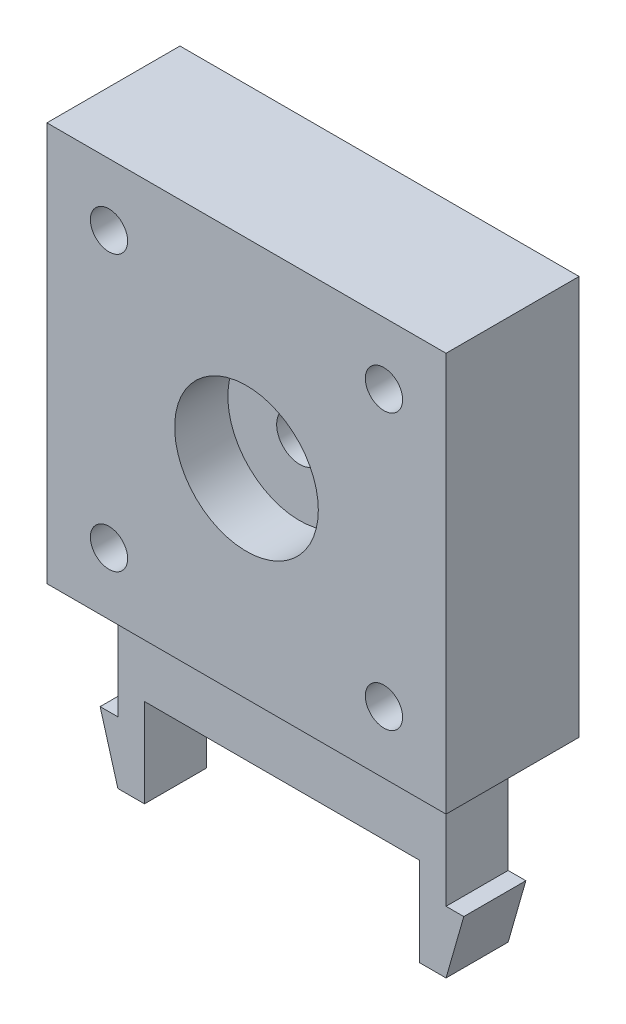
SolidWorks part; units mm, degrees
ref_plane "Front Plane" through (0, 0, 0) normal (0, 0, 1) x (1, 0, 0)
ref_plane "Top Plane" through (0, 0, 0) normal (0, 1, 0) x (1, 0, 0)
ref_plane "Right Plane" through (0, 0, 0) normal (1, 0, 0) x (0, 0, -1)
sketch "Sketch1" plane through (0, 0, 0) normal (0, 0, 1) x (1, 0, 0)
  line L1 (22.5, -22.5) -> (-22.5, -22.5)
  line L2 (22.5, -22.5) -> (22.5, 22.5)
  line L3 (22.5, 22.5) -> (-22.5, 22.5)
  line L4 (-22.5, -22.5) -> (-22.5, 22.5)
  line L5 (22.5, -22.5) -> (-22.5, 22.5) construction
  line L6 (22.5, 22.5) -> (-22.5, -22.5) construction
  circle A0 centre (0, 0) radius 2.6
  point P0 (0, 0)
  dimension "D3" = 5.2
  dimension "D1" = 45
  dimension "D2" = 45
extrude "Boss-Extrude1" add sketch "Sketch1" along normal mid plane 15
sketch "Sketch2" plane through (0, 0, 7.5) normal (0, 0, 1) x (1, 0, 0)
  circle A0 centre (0, 0) radius 8.1
  dimension "D1" = 16.2
extrude "Cut-Extrude1" cut sketch "Sketch2" against normal blind 6
sketch "Sketch5" plane through (0, 0, -7.5) normal (0, 0, -1) x (-1, 0, 0)
  circle A0 centre (0, 0) radius 8.1
  dimension "D1" = 16.2
extrude "Cut-Extrude4" cut sketch "Sketch5" against normal blind 6
sketch "Sketch6" plane through (0, 0, -7.5) normal (0, 0, 1) x (1, 0, 0)
  line L0 (19.2, 17.6362) -> (15.5, 19.7724)
  line L1 (15.5, -15.5) -> (-15.5, -15.5) construction
  line L2 (15.5, -15.5) -> (15.5, 15.5) construction
  line L3 (15.5, 15.5) -> (-15.5, 15.5) construction
  line L4 (-15.5, -15.5) -> (-15.5, 15.5) construction
  line L5 (15.5, -15.5) -> (-15.5, 15.5) construction
  line L6 (15.5, 15.5) -> (-15.5, -15.5) construction
  line L7 (-11.8, 17.6362) -> (-15.5, 19.7724)
  line L8 (-15.5, 19.7724) -> (-19.2, 17.6362)
  line L9 (-19.2, 17.6362) -> (-19.2, 13.3638)
  line L10 (-19.2, 13.3638) -> (-15.5, 11.2276)
  line L11 (-15.5, 11.2276) -> (-11.8, 13.3638)
  line L12 (-11.8, 13.3638) -> (-11.8, 17.6362)
  line L13 (15.5, 19.7724) -> (11.8, 17.6362)
  line L14 (11.8, 17.6362) -> (11.8, 13.3638)
  line L15 (11.8, 13.3638) -> (15.5, 11.2276)
  line L16 (15.5, 11.2276) -> (19.2, 13.3638)
  line L17 (19.2, 13.3638) -> (19.2, 17.6362)
  line L18 (19.2, -13.3638) -> (15.5, -11.2276)
  line L19 (15.5, -11.2276) -> (11.8, -13.3638)
  line L20 (11.8, -13.3638) -> (11.8, -17.6362)
  line L21 (11.8, -17.6362) -> (15.5, -19.7724)
  line L22 (15.5, -19.7724) -> (19.2, -17.6362)
  line L23 (19.2, -17.6362) -> (19.2, -13.3638)
  line L24 (-11.8, -13.3638) -> (-15.5, -11.2276)
  line L25 (-15.5, -11.2276) -> (-19.2, -13.3638)
  line L26 (-19.2, -13.3638) -> (-19.2, -17.6362)
  line L27 (-19.2, -17.6362) -> (-15.5, -19.7724)
  line L28 (-15.5, -19.7724) -> (-11.8, -17.6362)
  line L29 (-11.8, -17.6362) -> (-11.8, -13.3638)
  circle A4 centre (-15.5, 15.5) radius 3.7 construction
  circle A5 centre (15.5, 15.5) radius 3.7 construction
  circle A6 centre (15.5, -15.5) radius 3.7 construction
  circle A7 centre (-15.5, -15.5) radius 3.7 construction
  point P0 (0, 0)
  dimension "D2" = 2
  dimension "D1" = 31
  dimension "D3" = 7.4
  dimension "D4" = 2
sketch "Sketch7" plane through (0, -22.5, 0) normal (0, -1, 0) x (1, 0, 0)
  line L1 (18.5, -3.5) -> (-18.5, -3.5)
  line L2 (18.5, -3.5) -> (18.5, 3.5)
  line L3 (18.5, 3.5) -> (-18.5, 3.5)
  line L4 (-18.5, -3.5) -> (-18.5, 3.5)
  line L5 (18.5, -3.5) -> (-18.5, 3.5) construction
  line L6 (18.5, 3.5) -> (-18.5, -3.5) construction
  point P0 (0, 0)
  dimension "D1" = 37
  dimension "D2" = 7
extrude "Boss-Extrude2" add sketch "Sketch7" along normal blind 10
extrude "Cut-Extrude6" cut sketch "Sketch6" along normal blind 3.6 from offset 2
sketch "Sketch8" plane through (0, 0, -7.5) normal (0, 0, -1) x (-1, 0, 0)
  line L1 (15.5, -15.5) -> (-15.5, -15.5) construction
  line L2 (15.5, -15.5) -> (15.5, 15.5) construction
  line L3 (15.5, 15.5) -> (-15.5, 15.5) construction
  line L4 (-15.5, -15.5) -> (-15.5, 15.5) construction
  line L5 (15.5, -15.5) -> (-15.5, 15.5) construction
  line L6 (15.5, 15.5) -> (-15.5, -15.5) construction
  circle A0 centre (-15.5, 15.5) radius 2.1
  circle A1 centre (15.5, 15.5) radius 2.1
  circle A2 centre (15.5, -15.5) radius 2.1
  circle A3 centre (-15.5, -15.5) radius 2.1
  point P0 (0, 0)
  dimension "D2" = 4.2
  dimension "D1" = 31
  dimension "D3" = 2
  dimension "D4" = 2
extrude "Cut-Extrude7" cut sketch "Sketch8" against normal through all from offset 2 offset against normal yes
sketch "Sketch9" plane through (0, -32.5, 0) normal (0, -1, 0) x (1, 0, 0)
  line L0 (-18.5, -3.5) -> (18.5, -3.5) construction
  line L1 (-18.5, 3.5) -> (-15.5, 3.5)
  line L2 (-18.5, 3.5) -> (-18.5, -3.5)
  line L3 (-18.5, -3.5) -> (-15.5, -3.5)
  line L4 (-15.5, 3.5) -> (-15.5, -3.5)
  line L5 (0, 3.5) -> (0, -3.5) construction
  line L6 (18.5, 3.5) -> (-18.5, 3.5) construction
  line L7 (-18.5, -3.5) -> (18.5, -3.5) construction
  line L8 (15.5, 3.5) -> (15.5, -3.5)
  line L9 (18.5, -3.5) -> (15.5, -3.5)
  line L10 (18.5, 3.5) -> (18.5, -3.5)
  line L11 (18.5, 3.5) -> (15.5, 3.5)
  dimension "D1" = 3
extrude "Boss-Extrude3" add sketch "Sketch9" along normal blind 10
sketch "Sketch10" plane through (-18.5, 0, 0) normal (-1, 0, 0) x (0, 0, 1)
  line L0 (3.5, -42.5) -> (3.5, -22.5) construction
  line L1 (-3.5, -42.5) -> (3.5, -42.5)
  line L2 (-3.5, -42.5) -> (-3.5, -35.5)
  line L3 (-3.5, -35.5) -> (3.5, -35.5)
  line L4 (3.5, -42.5) -> (3.5, -35.5)
  dimension "D1" = 7
extrude "Boss-Extrude4" add sketch "Sketch10" along normal blind 2
mirror "Mirror1" about plane through (0, 0, 0) normal (1, 0, 0) of "Boss-Extrude4"
chamfer "Chamfer2" distance 2 distance2 7 1 edges at (-20.5, -42.5, 0) first distance on face at (-18, -42.5, 0)
chamfer "Chamfer3" distance 7 distance2 2 1 edges at (20.5, -42.5, 0) first distance on face at (20.5, -39, 0)
